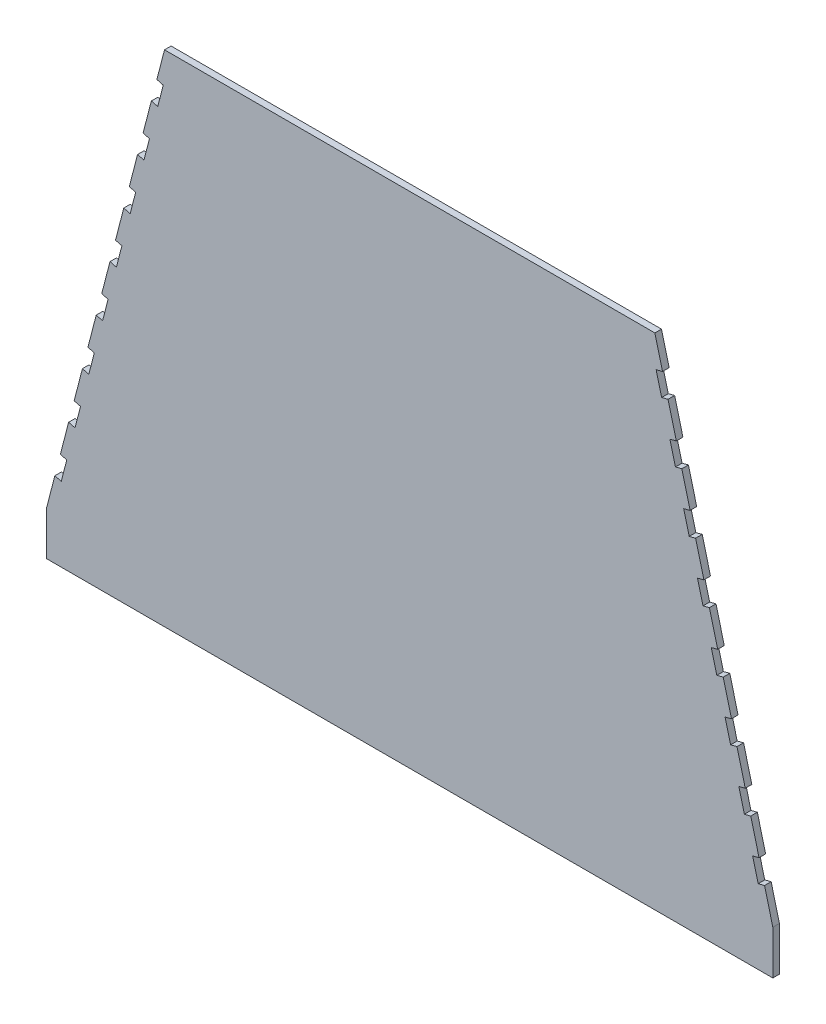
SolidWorks part; units mm, degrees
ref_plane "Front Plane" through (0, 0, 0) normal (0, 0, 1) x (1, 0, 0)
ref_plane "Top Plane" through (0, 0, 0) normal (0, 1, 0) x (1, 0, 0)
ref_plane "Right Plane" through (0, 0, 0) normal (1, 0, 0) x (0, 0, -1)
sketch "Sketch2" plane through (0, 0, 0) normal (0, 0, 1) x (1, 0, 0)
  line L0 (-111.4102, 164.3501) -> (111.4102, 164.3501)
  line L1 (111.4102, 164.3501) -> (165, -42.7051)
  line L2 (165, -42.7051) -> (-165, -42.7051)
  line L3 (-165, -42.7051) -> (-111.4102, 164.3501)
  line L4 (165, -42.7051) -> (165, -62.7051)
  line L5 (165, -62.7051) -> (-165, -62.7051)
  line L6 (-165, -62.7051) -> (-165, -42.7051)
  dimension "D1" = 330
  dimension "D2" = 213.8779
  dimension "D3" = 222.8203
  dimension "D4" = 20
extrude "Boss-Extrude1" add sketch "Sketch2" along normal blind 3 contours L3 L2 L1 L0 | L6 L5 L4 L2 region at (0, 54.1319, 0) region at (0, -52.7051, 0)
sketch "Sketch3" plane through (0, 0, 0) normal (0, 0, -1) x (-1, 0, 0)
  line L0 (-161.2416, -28.1836) -> (-158.3373, -28.9353)
  line L1 (-111.4102, 164.3501) -> (-165, -42.7051) construction
  line L2 (-158.3373, -28.9353) -> (-155.8316, -19.2543)
  line L3 (-155.8316, -19.2543) -> (-158.7359, -18.5026)
  line L4 (-158.7359, -18.5026) -> (-161.2416, -28.1836)
  dimension "D1" = 10
  dimension "D2" = 15
extrude "Cut-Extrude1" cut sketch "Sketch3" against normal blind 3
pattern_linear "LPattern1" count 8 spacing 25 along (-0.2506, 0.9681, 0) of "Cut-Extrude1"
mirror "Mirror1" about plane through (0, 0, 0) normal (1, 0, 0) of "LPattern1"
